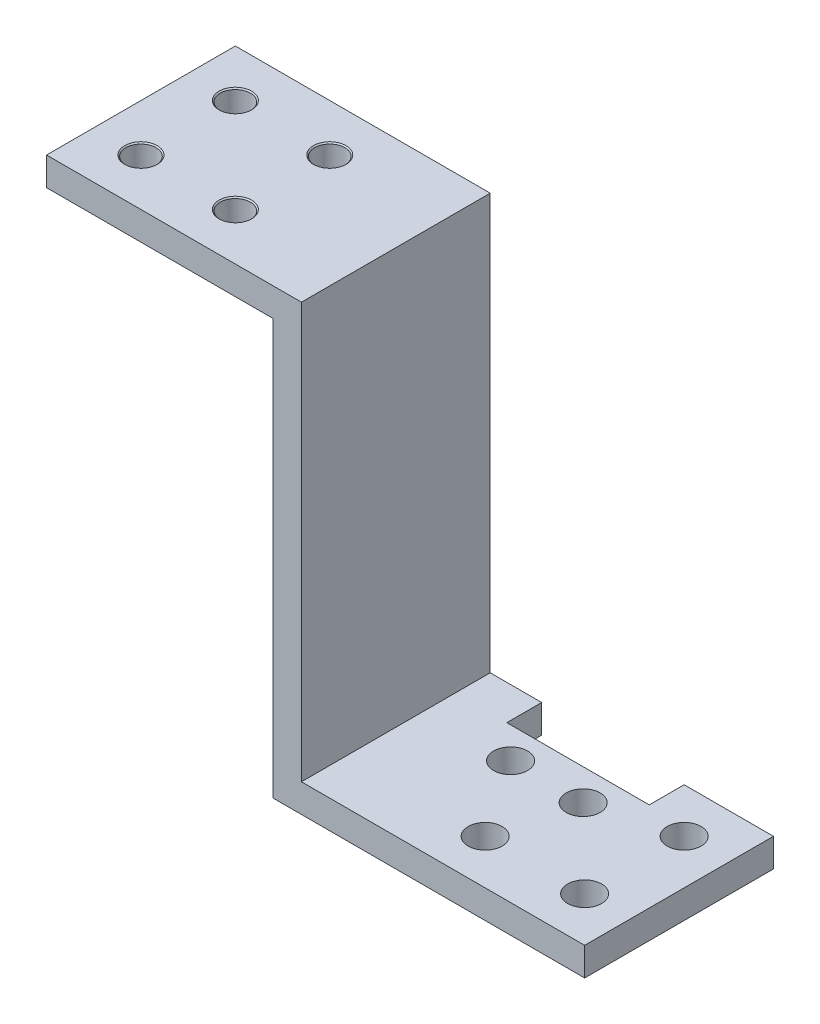
SolidWorks part; units mm, degrees
ref_plane "Front Plane" through (0, 0, 0) normal (0, 0, 1) x (1, 0, 0)
ref_plane "Top Plane" through (0, 0, 0) normal (0, 1, 0) x (1, 0, 0)
ref_plane "Right Plane" through (0, 0, 0) normal (1, 0, 0) x (0, 0, -1)
sketch "Sketch1" plane through (0, 0, 0) normal (0, 0, 1) x (1, 0, 0)
  line L0 (0, 44) -> (24, 44)
  line L1 (24, 44) -> (24, 0)
  line L2 (24, 0) -> (57, 0)
  line L3 (57, 0) -> (57, 3)
  line L4 (57, 3) -> (27, 3)
  line L5 (27, 3) -> (27, 47)
  line L6 (27, 47) -> (0, 47)
  line L7 (0, 47) -> (0, 44)
  line L8 (24, 25) -> (27, 25) construction
  point P12 (27, 25)
  dimension "D1" = 3
  dimension "D2" = 24
  dimension "D3" = 44
  dimension "D4" = 30
extrude "Boss-Extrude1" add sketch "Sketch1" along normal blind 20
hole_wizard "M3 Clearance Hole1" positions "Sketch2" profile "Sketch3" hole size "M3" standard "ANSI Metric" end condition through all
sketch "Sketch2" plane through (0, 47, 0) normal (0, 1, 0) x (1, 0, 0)
  line L0 (0, -10) -> (20, -10) construction
  line L1 (0, -20) -> (0, 0) construction
  line L4 (10, 0) -> (10, -20) construction
  line L7 (24, -20) -> (24, 0) construction
  line L8 (24, -20) -> (24, 0) construction
  line L9 (27, -20) -> (0, -20) construction
  point P17 (5, -5)
  point P25 (5, -15)
  point P26 (15, -5)
  point P27 (15, -15)
  point P37 (10, -10)
  dimension "D1" = 5
  dimension "D2" = 5
  dimension "D3" = 20
sketch "Sketch3" plane through (15, 47, 15) normal (1, 0, 0) x (0, 0, 1)
  line L0 (0, 0) -> (0, 47)
  line L1 (0, 47) -> (1.6, 47)
  line L2 (1.6, 47) -> (1.6, 0.125)
  line L3 (1.6, 0.125) -> (1.725, 0)
  line L5 (1.725, 0) -> (0, 0)
  line L6 (-1.6, 0.125) -> (-1.725, 0) construction
  line L11 (0, -6.35) -> (0, 107.95) construction
  dimension "Thru Hole Dia." = 3.2
  dimension "Thru Hole Depth" = 47
  dimension "Near C'Sink Dia." = 3.45
  dimension "Near C'Sink Angle" = 90
sketch "Sketch4" plane through (0, 3, 0) normal (0, 1, 0) x (1, 0, 0)
  line L0 (57, 0) -> (27, 0) construction
  line L1 (32.4508, 0) -> (47.5398, 0)
  line L2 (32.4508, 0) -> (32.4508, -3.6956)
  line L3 (32.4508, -3.6956) -> (47.5398, -3.6956)
  line L4 (47.5398, 0) -> (47.5398, -3.6956)
  line L5 (32.6508, -10.4956) -> (32.6508, -3.4956) construction
  line L6 (47.3398, -10.4956) -> (47.3398, -3.4956) construction
  line L7 (32.6508, -10.4956) -> (32.6508, -3.4956) construction
  line L8 (47.3398, -10.4956) -> (47.3398, -3.4956) construction
  line L9 (32.6508, -3.4956) -> (47.3398, -3.4956) construction
  point P10 (39.9953, -3.6956)
  point P11 (39.9953, -3.4956)
  dimension "D1" = 0.2
  dimension "D2" = 0.2
extrude "Cut-Extrude1" cut sketch "Sketch4" against normal through all
sketch "Sketch5" plane through (0, 3, 0) normal (0, 1, 0) x (1, 0, 0)
  point P0 (36.1508, -6.9956)
  point P3 (43.8398, -6.9956)
hole_wizard "M3 Clearance Hole2" positions "Sketch5" profile "Sketch6" hole size "M3" standard "ANSI Metric" end condition through all
sketch "Sketch6" plane through (36.1508, 3, 6.9956) normal (1, 0, 0) x (0, 0, 1)
  line L0 (0, 0) -> (0, 3)
  line L1 (0, 3) -> (1.8, 3)
  line L2 (1.8, 3) -> (1.8, 0)
  line L5 (1.8, 0) -> (0, 0)
  line L11 (0, -6.35) -> (0, 107.95) construction
  dimension "Thru Hole Dia." = 3.6
  dimension "Thru Hole Depth" = 3
sketch "Sketch9" plane through (0, 3, 0) normal (0, 1, 0) x (1, 0, 0)
  line L0 (57, -20) -> (27, -20) construction
  line L1 (57, -20) -> (57, 0) construction
  line L2 (57, 0) -> (47.5398, 0) construction
  line L3 (47.5398, -3.6956) -> (47.5398, 0) construction
  line L4 (57, -20) -> (27, -20)
  line L5 (57, -20) -> (57, 0)
  line L6 (57, 0) -> (47.5398, 0)
  line L7 (47.5398, -3.6956) -> (47.5398, 0)
  line L8 (47.5398, -3.6956) -> (47.5398, -10.5398)
  line L9 (47.5398, -10.5398) -> (37, -10.5398)
  line L10 (37, -10.5398) -> (37, -20)
  line L11 (52.2699, 0) -> (52.2699, -4.7301) construction
  line L12 (52.2699, -4.7301) -> (52.2699, -15.2699) construction
  line L13 (52.2699, -15.2699) -> (52.2699, -20) construction
  line L14 (37, -15.2699) -> (41.7301, -15.2699) construction
  line L15 (41.7301, -15.2699) -> (52.2699, -15.2699) construction
  line L16 (52.2699, -15.2699) -> (57, -15.2699) construction
  circle A0 centre (52.2699, -4.7301) radius 1.75
  circle A1 centre (52.2699, -15.2699) radius 1.75
  circle A2 centre (41.7301, -15.2699) radius 1.75
  point P11 (52.2699, 0)
  point P17 (42.0697, -16.2523)
  point P18 (37, -15.2699)
  point P21 (41.7114, -15.2699)
  dimension "D1" = 3.5
  dimension "D2" = 3.5
  dimension "D3" = 3.5
sketch "Sketch10" plane through (0, 3, 0) normal (0, 1, 0) x (1, 0, 0)
  point P0 (41.7301, -15.2699)
  point P3 (52.2699, -15.2699)
  point P6 (52.2699, -4.7301)
hole_wizard "M3 Clearance Hole3" positions "Sketch10" profile "Sketch11" hole size "M3" standard "ANSI Metric" end condition through all
sketch "Sketch11" plane through (41.7301, 3, 15.2699) normal (1, 0, 0) x (0, 0, 1)
  line L0 (0, 0) -> (0, 3)
  line L1 (0, 3) -> (1.8, 3)
  line L2 (1.8, 3) -> (1.8, 0)
  line L5 (1.8, 0) -> (0, 0)
  line L11 (0, -6.35) -> (0, 107.95) construction
  dimension "Thru Hole Dia." = 3.6
  dimension "Thru Hole Depth" = 3
